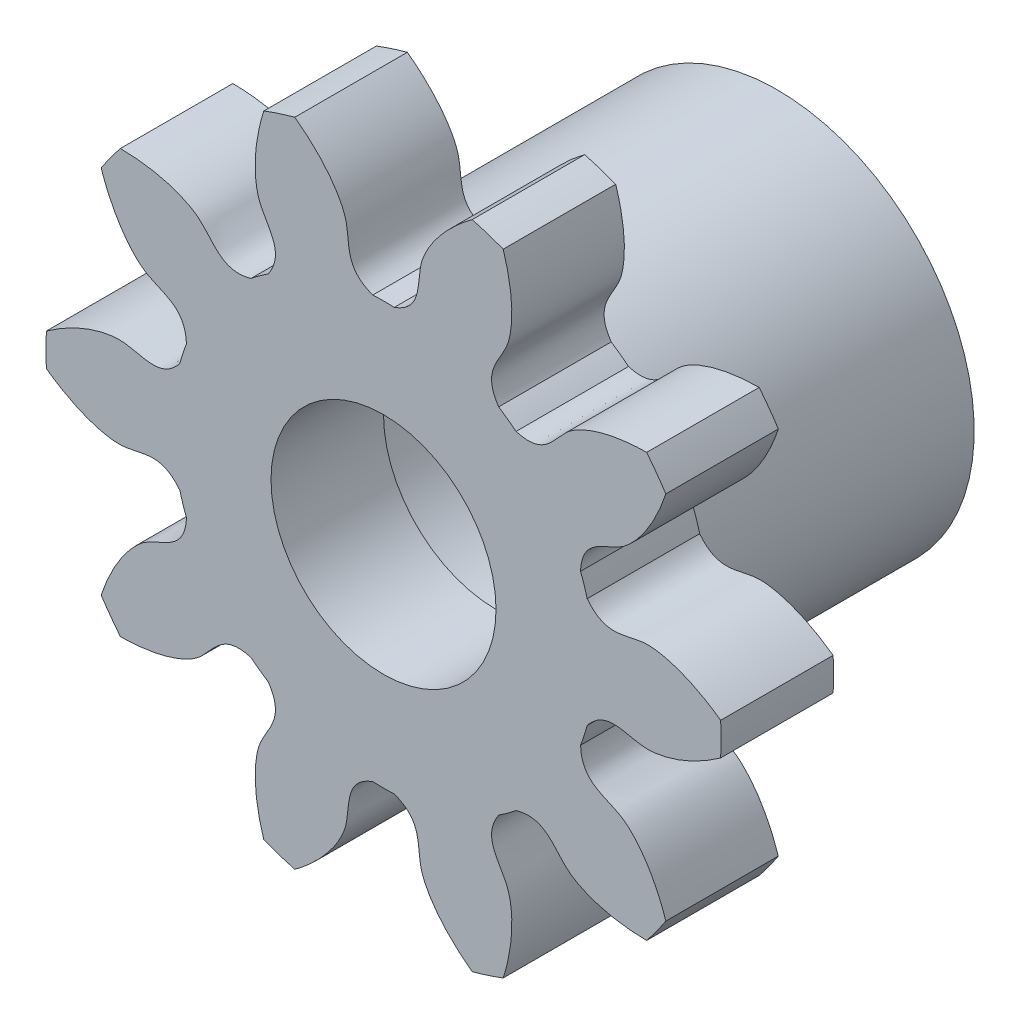
SolidWorks part; units mm, degrees
ref_plane "前视基准面" through (0, 0, 0) normal (0, 0, 1) x (1, 0, 0)
ref_plane "上视基准面" through (0, 0, 0) normal (0, 1, 0) x (1, 0, 0)
ref_plane "右视基准面" through (0, 0, 0) normal (1, 0, 0) x (0, 0, -1)
sketch "草图1" plane through (0, 0, 0) normal (0, 0, 1) x (1, 0, 0)
  circle A0 centre (0, 0) radius 12
extrude "凸台-拉伸1" add sketch "草图1" along normal blind 30
ref_axis "基准轴1" through (0, 0, -1.5) along (0, 0, 1)
sketch "草图2" plane through (0, 0, 0) normal (0, 0, 1) x (1, 0, 0)
  line L0 (0, 0) -> (0, 12) construction
  circle A0 centre (0, 0) radius 12 construction
  arc A1 (0.3809, 7.4903) -> (-0.3809, 7.4903) centre (0, 0) ccw
  arc A2 (8.5072, 13.3886) -> (-8.5072, 13.3886) centre (0, 0) ccw
  spline S0 degree 3 poles (0.3809, 7.4903) (1.4509, 7.8811) (1.1477, 8.7412) (1.3773, 9.4493) (1.389, 9.4831) (1.4027, 9.5201) (1.4184, 9.5604) (1.4364, 9.6038) (1.4568, 9.6502) (1.4797, 9.6997) (1.5052, 9.7521) (1.5335, 9.8073) (1.5646, 9.8653) (1.5987, 9.9258) (1.636, 9.989) (1.6765, 10.0545) (1.7203, 10.1225) (1.7675, 10.1926) (1.8184, 10.2648) (1.8728, 10.3391) (1.9311, 10.4152) (1.9932, 10.4931) (2.0592, 10.5726) (2.1293, 10.6537) (2.2035, 10.7361) (2.2819, 10.8197) (2.3646, 10.9045) (2.4516, 10.9902) (2.5431, 11.0768) (2.639, 11.164) (2.7395, 11.2518) (2.8447, 11.3399) (2.9545, 11.4283) (3.069, 11.5168) (3.1883, 11.6052) (3.3124, 11.6934) (3.4413, 11.7812) (3.5751, 11.8685) (3.7138, 11.9551) (3.8575, 12.0408) (4.0061, 12.1254) (4.1597, 12.2089) (4.3182, 12.291) (4.4818, 12.3716) (4.6503, 12.4505) (4.8238, 12.5275) (5.0022, 12.6025) (5.1856, 12.6753) (5.374, 12.7458) (5.5673, 12.8137) (5.7655, 12.8789) (5.9685, 12.9412) (6.1763, 13.0005) (6.389, 13.0566) (6.6063, 13.1093) (6.8284, 13.1585) (7.055, 13.2039) (7.2863, 13.2455) (7.522, 13.283) (7.7621, 13.3164) (8.0906, 13.3553) (8.3397, 13.3772) (8.5072, 13.3886) knots 0 0 0 0 0.201721 0.204697 0.208023 0.211699 0.215726 0.220102 0.224829 0.229906 0.235332 0.241109 0.247237 0.253714 0.260541 0.267719 0.275246 0.283124 0.291352 0.29993 0.308858 0.318136 0.327765 0.337743 0.348072 0.358751 0.36978 0.381158 0.392888 0.404967 0.417396 0.430176 0.443305 0.456785 0.470615 0.484795 0.499325 0.514205 0.529435 0.545016 0.560946 0.577227 0.593858 0.610839 0.62817 0.645851 0.663882 0.682264 0.700995 0.720077 0.739509 0.759291 0.779423 0.799905 0.820737 0.84192 0.863452 0.885335 0.907568 0.930151 0.953084 1 1 1 1
  spline S1 degree 3 poles (-0.3809, 7.4903) (-1.4509, 7.8811) (-1.1477, 8.7412) (-1.3773, 9.4493) (-1.389, 9.4831) (-1.4027, 9.5201) (-1.4184, 9.5604) (-1.4364, 9.6038) (-1.4568, 9.6502) (-1.4797, 9.6997) (-1.5052, 9.7521) (-1.5335, 9.8073) (-1.5646, 9.8653) (-1.5987, 9.9258) (-1.636, 9.989) (-1.6765, 10.0545) (-1.7203, 10.1225) (-1.7675, 10.1926) (-1.8184, 10.2648) (-1.8728, 10.3391) (-1.9311, 10.4152) (-1.9932, 10.4931) (-2.0592, 10.5726) (-2.1293, 10.6537) (-2.2035, 10.7361) (-2.2819, 10.8197) (-2.3646, 10.9045) (-2.4516, 10.9902) (-2.5431, 11.0768) (-2.639, 11.164) (-2.7395, 11.2518) (-2.8447, 11.3399) (-2.9545, 11.4283) (-3.069, 11.5168) (-3.1883, 11.6052) (-3.3124, 11.6934) (-3.4413, 11.7812) (-3.5751, 11.8685) (-3.7138, 11.9551) (-3.8575, 12.0408) (-4.0061, 12.1254) (-4.1597, 12.2089) (-4.3182, 12.291) (-4.4818, 12.3716) (-4.6503, 12.4505) (-4.8238, 12.5275) (-5.0022, 12.6025) (-5.1856, 12.6753) (-5.374, 12.7458) (-5.5673, 12.8137) (-5.7655, 12.8789) (-5.9685, 12.9412) (-6.1763, 13.0005) (-6.389, 13.0566) (-6.6063, 13.1093) (-6.8284, 13.1585) (-7.055, 13.2039) (-7.2863, 13.2455) (-7.522, 13.283) (-7.7621, 13.3164) (-8.0906, 13.3553) (-8.3397, 13.3772) (-8.5072, 13.3886) knots 0 0 0 0 0.201721 0.204697 0.208023 0.211699 0.215726 0.220102 0.224829 0.229906 0.235332 0.241109 0.247237 0.253714 0.260541 0.267719 0.275246 0.283124 0.291352 0.29993 0.308858 0.318136 0.327765 0.337743 0.348072 0.358751 0.36978 0.381158 0.392888 0.404967 0.417396 0.430176 0.443305 0.456785 0.470615 0.484795 0.499325 0.514205 0.529435 0.545016 0.560946 0.577227 0.593858 0.610839 0.62817 0.645851 0.663882 0.682264 0.700995 0.720077 0.739509 0.759291 0.779423 0.799905 0.820737 0.84192 0.863452 0.885335 0.907568 0.930151 0.953084 1 1 1 1
extrude "切除-拉伸1" cut sketch "草图2" along normal through all
pattern_circular "阵列(圆周)1" count 10 every 36 about axis through (0, 0, -1.5) along (0, 0, 1) of "切除-拉伸1"
sketch "草图3" plane through (0, 0, 0) normal (0, 0, 1) x (1, 0, 0)
  circle A0 centre (0, 0) radius 10 construction
  arc A21 (-4.0945, 6.2837) -> (-4.7109, 5.8359) centre (0, 0) ccw
  arc A22 (-9.3561, 7.5142) -> (-10.0376, 6.5762) centre (0, 0) ccw
  arc A23 (-7.006, 2.6769) -> (-7.2414, 1.9524) centre (0, 0) ccw
  arc A24 (-11.986, 0.5797) -> (-11.986, -0.5797) centre (0, 0) ccw
  arc A25 (-7.2414, -1.9524) -> (-7.006, -2.6769) centre (0, 0) ccw
  arc A26 (-10.0376, -6.5762) -> (-9.3561, -7.5142) centre (0, 0) ccw
  arc A27 (-4.7109, -5.8359) -> (-4.0945, -6.2837) centre (0, 0) ccw
  arc A28 (-4.2552, -11.2202) -> (-3.1525, -11.5785) centre (0, 0) ccw
  arc A29 (-0.3809, -7.4903) -> (0.3809, -7.4903) centre (0, 0) ccw
  arc A30 (3.1525, -11.5785) -> (4.2552, -11.2202) centre (0, 0) ccw
  arc A31 (4.0945, -6.2837) -> (4.7109, -5.8359) centre (0, 0) ccw
  arc A32 (9.3561, -7.5142) -> (10.0376, -6.5762) centre (0, 0) ccw
  arc A33 (7.006, -2.6769) -> (7.2414, -1.9524) centre (0, 0) ccw
  arc A34 (11.986, -0.5797) -> (11.986, 0.5797) centre (0, 0) ccw
  arc A35 (7.2414, 1.9524) -> (7.006, 2.6769) centre (0, 0) ccw
  arc A36 (10.0376, 6.5762) -> (9.3561, 7.5142) centre (0, 0) ccw
  arc A37 (4.7109, 5.8359) -> (4.0945, 6.2837) centre (0, 0) ccw
  arc A38 (4.2552, 11.2202) -> (3.1525, 11.5785) centre (0, 0) ccw
  arc A39 (0.3809, 7.4903) -> (-0.3809, 7.4903) centre (0, 0) ccw
  arc A40 (-3.1525, 11.5785) -> (-4.2552, 11.2202) centre (0, 0) ccw
  arc A41 (-4.0945, 6.2837) -> (-4.7109, 5.8359) centre (0, 0) ccw
  arc A42 (-9.3561, 7.5142) -> (-10.0376, 6.5762) centre (0, 0) ccw
  arc A43 (-7.006, 2.6769) -> (-7.2414, 1.9524) centre (0, 0) ccw
  arc A44 (-11.986, 0.5797) -> (-11.986, -0.5797) centre (0, 0) ccw
  arc A45 (-7.2414, -1.9524) -> (-7.006, -2.6769) centre (0, 0) ccw
  arc A46 (-10.0376, -6.5762) -> (-9.3561, -7.5142) centre (0, 0) ccw
  arc A47 (-4.7109, -5.8359) -> (-4.0945, -6.2837) centre (0, 0) ccw
  arc A48 (-4.2552, -11.2202) -> (-3.1525, -11.5785) centre (0, 0) ccw
  arc A49 (-0.3809, -7.4903) -> (0.3809, -7.4903) centre (0, 0) ccw
  arc A50 (3.1525, -11.5785) -> (4.2552, -11.2202) centre (0, 0) ccw
  arc A51 (4.0945, -6.2837) -> (4.7109, -5.8359) centre (0, 0) ccw
  arc A52 (9.3561, -7.5142) -> (10.0376, -6.5762) centre (0, 0) ccw
  arc A53 (7.006, -2.6769) -> (7.2414, -1.9524) centre (0, 0) ccw
  arc A54 (11.986, -0.5797) -> (11.986, 0.5797) centre (0, 0) ccw
  arc A55 (7.2414, 1.9524) -> (7.006, 2.6769) centre (0, 0) ccw
  arc A56 (10.0376, 6.5762) -> (9.3561, 7.5142) centre (0, 0) ccw
  arc A57 (4.7109, 5.8359) -> (4.0945, 6.2837) centre (0, 0) ccw
  arc A58 (4.2552, 11.2202) -> (3.1525, 11.5785) centre (0, 0) ccw
  arc A59 (0.3809, 7.4903) -> (-0.3809, 7.4903) centre (0, 0) ccw
  arc A60 (-3.1525, 11.5785) -> (-4.2552, 11.2202) centre (0, 0) ccw
  spline S20 degree 3 poles (2357.9896, 3233.0149) (-45.5111, -76.1208) (0.8912, 1.3359) (-6.6791, 6.8428) (-6.7335, 6.8799) (-6.81, 6.9276) (-6.9015, 6.9798) (-7.0083, 7.0352) (-7.1308, 7.0926) (-7.2694, 7.151) (-7.4243, 7.2091) (-7.5956, 7.2657) (-7.7836, 7.3195) (-7.9881, 7.3693) (-8.2093, 7.4139) (-8.4468, 7.452) (-8.7007, 7.4824) (-8.9705, 7.5038) (-41.9663, 8.7956) (-79.134, -211.6177) (2738.2164, 2912.7683) knots -1.870678 -1.870678 -1.870678 -1.870678 0.735149 0.738125 0.745127 0.75353 0.763333 0.774537 0.787142 0.801147 0.816552 0.833358 0.851564 0.871171 0.892178 0.914586 0.938395 0.963603 0.990213 10.164096 10.164096 10.164096 10.164096 only from (-4.7109, 5.8359) to (-9.3561, 7.5142)
  spline S21 degree 3 poles (-1900.4629, -3517.2649) (168.6597, 144.2035) (-22.0225, 35.4119) (-9.8048, 5.9626) (-9.6975, 5.7306) (-9.5878, 5.5164) (-9.4771, 5.3199) (-9.3665, 5.1408) (-9.2572, 4.9787) (-9.1505, 4.8332) (-9.0474, 4.7038) (-8.9491, 4.5901) (-8.8565, 4.4913) (-8.7709, 4.4068) (-8.693, 4.336) (-8.6239, 4.2779) (-8.5719, 4.2376) (-0.9951, -1.2604) (58.3315, 66.8063) (-2346.1255, -3241.6441) knots -8.822355 -8.822355 -8.822355 -8.822355 0.036397 0.061605 0.085414 0.107822 0.128829 0.148436 0.166642 0.183448 0.198853 0.212858 0.225463 0.236667 0.24647 0.254873 0.261875 0.264851 2.87068 2.87068 2.87068 2.87068 only from (-10.0376, 6.5762) to (-7.006, 2.6769)
  spline S22 degree 3 poles (7.3352, 4001.5555) (7.9234, -88.3337) (-0.0642, 1.6046) (-9.4256, 1.6101) (-9.4914, 1.6081) (-9.5814, 1.6018) (-9.686, 1.5902) (-9.805, 1.5722) (-9.9379, 1.5467) (-10.0843, 1.5125) (-10.2438, 1.4684) (-10.4157, 1.4134) (-10.5993, 1.3465) (-10.7941, 1.2666) (-10.9992, 1.1727) (-11.2138, 1.0639) (-11.437, 0.9392) (-11.6679, 0.7979) (-39.1213, -17.5514) (60.365, -217.7161) (503.1813, 3965.9623) knots -1.870678 -1.870678 -1.870678 -1.870678 0.735149 0.738125 0.745127 0.75353 0.763333 0.774537 0.787142 0.801147 0.816552 0.833358 0.851564 0.871171 0.892178 0.914586 0.938395 0.963603 0.990213 10.164096 10.164096 10.164096 10.164096 only from (-7.2414, 1.9524) to (-11.986, 0.5797)
  spline S23 degree 3 poles (529.8897, -3962.5911) (51.6878, 215.7988) (-38.6312, 15.7043) (-11.437, -0.9392) (-11.2138, -1.0639) (-10.9992, -1.1727) (-10.7941, -1.2666) (-10.5993, -1.3465) (-10.4157, -1.4134) (-10.2438, -1.4684) (-10.0843, -1.5125) (-9.9379, -1.5467) (-9.805, -1.5722) (-9.686, -1.5902) (-9.5814, -1.6018) (-9.4914, -1.6081) (-9.4256, -1.6101) (-0.0642, -1.6046) (7.9234, 88.3338) (7.3352, -4001.5632) knots -8.822355 -8.822355 -8.822355 -8.822355 0.036397 0.061605 0.085414 0.107822 0.128829 0.148436 0.166642 0.183448 0.198853 0.212858 0.225463 0.236667 0.24647 0.254873 0.261875 0.264851 2.87068 2.87068 2.87068 2.87068 only from (-11.986, -0.5797) to (-7.2414, -1.9524)
  spline S24 degree 3 poles (-2346.121, 3241.6379) (58.3315, -66.8062) (-0.9952, 1.2604) (-8.5719, -4.2376) (-8.6239, -4.2779) (-8.693, -4.336) (-8.7709, -4.4068) (-8.8565, -4.4913) (-8.9491, -4.5901) (-9.0474, -4.7038) (-9.1505, -4.8332) (-9.2572, -4.9787) (-9.3665, -5.1408) (-9.4771, -5.3199) (-9.5878, -5.5164) (-9.6975, -5.7306) (-9.8048, -5.9626) (-9.9085, -6.2127) (-21.3334, -37.1943) (176.8067, -140.6544) (-1924.0519, 3504.2934) knots -1.870678 -1.870678 -1.870678 -1.870678 0.735149 0.738125 0.745127 0.75353 0.763333 0.774537 0.787142 0.801147 0.816552 0.833358 0.851564 0.871171 0.892178 0.914586 0.938395 0.963603 0.990213 10.164096 10.164096 10.164096 10.164096 only from (-7.006, -2.6769) to (-10.0376, -6.5762)
  spline S25 degree 3 poles (2757.8424, -2894.3422) (-85.027, 204.9662) (-40.4841, -10.0018) (-8.7007, -7.4824) (-8.4468, -7.452) (-8.2093, -7.4139) (-7.9881, -7.3693) (-7.7836, -7.3195) (-7.5956, -7.2657) (-7.4243, -7.2091) (-7.2694, -7.151) (-7.1308, -7.0926) (-7.0083, -7.0352) (-6.9015, -6.9798) (-6.81, -6.9277) (-6.7335, -6.8799) (-6.6791, -6.8428) (0.8912, -1.3359) (-45.5111, 76.1209) (2357.9941, -3233.0211) knots -8.822355 -8.822355 -8.822355 -8.822355 0.036397 0.061605 0.085414 0.107822 0.128829 0.148436 0.166642 0.183448 0.198853 0.212858 0.225463 0.236667 0.24647 0.254873 0.261875 0.264851 2.87068 2.87068 2.87068 2.87068 only from (-9.3561, -7.5142) to (-4.7109, -5.8359)
  spline S26 degree 3 poles (-3803.4388, 1243.5248) (86.4588, -19.761) (-1.546, 0.4348) (-4.444, -8.4668) (-4.4624, -8.5299) (-4.4842, -8.6175) (-4.5055, -8.7206) (-4.5252, -8.8393) (-4.542, -8.9735) (-4.5547, -9.1234) (-4.562, -9.2886) (-4.5629, -9.4691) (-4.556, -9.6645) (-4.5402, -9.8744) (-4.5142, -10.0985) (-4.4771, -10.3362) (-4.4275, -10.587) (-4.3645, -10.8503) (4.6032, -42.6303) (225.7141, -9.8674) (-3616.3627, 1704.1036) knots -1.870678 -1.870678 -1.870678 -1.870678 0.735149 0.738125 0.745127 0.75353 0.763333 0.774537 0.787142 0.801147 0.816552 0.833358 0.851564 0.871171 0.892178 0.914586 0.938395 0.963603 0.990213 10.164096 10.164096 10.164096 10.164096 only from (-4.0945, -6.2837) to (-4.2552, -11.2202)
  spline S27 degree 3 poles (3932.393, -720.553) (-189.2644, 115.8435) (-26.8734, -31.8875) (-2.641, -11.1675) (-2.4534, -10.9937) (-2.2836, -10.8233) (-2.131, -10.6572) (-1.9948, -10.4967) (-1.8744, -10.3427) (-1.769, -10.1962) (-1.6778, -10.0581) (-1.6, -9.9295) (-1.5346, -9.8109) (-1.4808, -9.7034) (-1.4375, -9.6074) (-1.4036, -9.5238) (-1.3814, -9.4619) (1.5063, -0.5569) (-81.562, 34.8323) (3807.9794, -1229.5749) knots -8.822355 -8.822355 -8.822355 -8.822355 0.036397 0.061605 0.085414 0.107822 0.128829 0.148436 0.166642 0.183448 0.198853 0.212858 0.225463 0.236667 0.24647 0.254873 0.261875 0.264851 2.87068 2.87068 2.87068 2.87068 only from (-3.1525, -11.5785) to (-0.3809, -7.4903)
  spline S28 degree 3 poles (-3807.9721, -1229.5725) (81.5619, 34.8323) (-1.5063, -0.557) (1.3814, -9.4619) (1.4036, -9.5238) (1.4375, -9.6074) (1.4808, -9.7034) (1.5346, -9.8109) (1.6, -9.9295) (1.6778, -10.0581) (1.769, -10.1962) (1.8744, -10.3427) (1.9948, -10.4967) (2.131, -10.6572) (2.2836, -10.8233) (2.4534, -10.9937) (2.641, -11.1675) (2.8467, -11.3434) (28.7815, -31.7829) (188.4065, 124.6885) (-3927.3458, -746.9958) knots -1.870678 -1.870678 -1.870678 -1.870678 0.735149 0.738125 0.745127 0.75353 0.763333 0.774537 0.787142 0.801147 0.816552 0.833358 0.851564 0.871171 0.892178 0.914586 0.938395 0.963603 0.990213 10.164096 10.164096 10.164096 10.164096 only from (0.3809, -7.4903) to (3.1525, -11.5785)
  spline S29 degree 3 poles (3604.9032, 1728.463) (-221.2093, -17.5274) (-2.998, -41.5933) (4.4275, -10.587) (4.4771, -10.3362) (4.5142, -10.0985) (4.5402, -9.8744) (4.556, -9.6645) (4.5629, -9.4691) (4.562, -9.2886) (4.5547, -9.1234) (4.542, -8.9735) (4.5252, -8.8393) (4.5055, -8.7206) (4.4842, -8.6175) (4.4624, -8.5299) (4.444, -8.4668) (1.5459, 0.4348) (-86.459, -19.761) (3803.446, 1243.5272) knots -8.822355 -8.822355 -8.822355 -8.822355 0.036397 0.061605 0.085414 0.107822 0.128829 0.148436 0.166642 0.183448 0.198853 0.212858 0.225463 0.236667 0.24647 0.254873 0.261875 0.264851 2.87068 2.87068 2.87068 2.87068 only from (4.2552, -11.2202) to (4.0945, -6.2837)
  spline S30 degree 3 poles (-2357.9896, -3233.0149) (45.5111, 76.1208) (-0.8912, -1.3359) (6.6791, -6.8428) (6.7335, -6.8799) (6.81, -6.9276) (6.9015, -6.9798) (7.0083, -7.0352) (7.1308, -7.0926) (7.2694, -7.151) (7.4243, -7.2091) (7.5956, -7.2657) (7.7836, -7.3195) (7.9881, -7.3693) (8.2093, -7.4139) (8.4468, -7.452) (8.7007, -7.4824) (8.9705, -7.5038) (41.9663, -8.7956) (79.134, 211.6177) (-2738.2164, -2912.7683) knots -1.870678 -1.870678 -1.870678 -1.870678 0.735149 0.738125 0.745127 0.75353 0.763333 0.774537 0.787142 0.801147 0.816552 0.833358 0.851564 0.871171 0.892178 0.914586 0.938395 0.963603 0.990213 10.164096 10.164096 10.164096 10.164096 only from (4.7109, -5.8359) to (9.3561, -7.5142)
  spline S31 degree 3 poles (1900.4629, 3517.2649) (-168.6597, -144.2035) (22.0225, -35.4119) (9.8048, -5.9626) (9.6975, -5.7306) (9.5878, -5.5164) (9.4771, -5.3199) (9.3665, -5.1408) (9.2572, -4.9787) (9.1505, -4.8332) (9.0474, -4.7038) (8.9491, -4.5901) (8.8565, -4.4913) (8.7709, -4.4068) (8.693, -4.336) (8.6239, -4.2779) (8.5719, -4.2376) (0.9951, 1.2604) (-58.3315, -66.8063) (2346.1255, 3241.6441) knots -8.822355 -8.822355 -8.822355 -8.822355 0.036397 0.061605 0.085414 0.107822 0.128829 0.148436 0.166642 0.183448 0.198853 0.212858 0.225463 0.236667 0.24647 0.254873 0.261875 0.264851 2.87068 2.87068 2.87068 2.87068 only from (10.0376, -6.5762) to (7.006, -2.6769)
  spline S32 degree 3 poles (-7.3352, -4001.5555) (-7.9234, 88.3337) (0.0642, -1.6046) (9.4256, -1.6101) (9.4914, -1.6081) (9.5814, -1.6018) (9.686, -1.5902) (9.805, -1.5722) (9.9379, -1.5467) (10.0843, -1.5125) (10.2438, -1.4684) (10.4157, -1.4134) (10.5993, -1.3465) (10.7941, -1.2666) (10.9992, -1.1727) (11.2138, -1.0639) (11.437, -0.9392) (11.6679, -0.7979) (39.1213, 17.5514) (-60.365, 217.7161) (-503.1813, -3965.9623) knots -1.870678 -1.870678 -1.870678 -1.870678 0.735149 0.738125 0.745127 0.75353 0.763333 0.774537 0.787142 0.801147 0.816552 0.833358 0.851564 0.871171 0.892178 0.914586 0.938395 0.963603 0.990213 10.164096 10.164096 10.164096 10.164096 only from (7.2414, -1.9524) to (11.986, -0.5797)
  spline S33 degree 3 poles (-529.8897, 3962.5911) (-51.6878, -215.7988) (38.6312, -15.7043) (11.437, 0.9392) (11.2138, 1.0639) (10.9992, 1.1727) (10.7941, 1.2666) (10.5993, 1.3465) (10.4157, 1.4134) (10.2438, 1.4684) (10.0843, 1.5125) (9.9379, 1.5467) (9.805, 1.5722) (9.686, 1.5902) (9.5814, 1.6018) (9.4914, 1.6081) (9.4256, 1.6101) (0.0642, 1.6046) (-7.9234, -88.3338) (-7.3352, 4001.5632) knots -8.822355 -8.822355 -8.822355 -8.822355 0.036397 0.061605 0.085414 0.107822 0.128829 0.148436 0.166642 0.183448 0.198853 0.212858 0.225463 0.236667 0.24647 0.254873 0.261875 0.264851 2.87068 2.87068 2.87068 2.87068 only from (11.986, 0.5797) to (7.2414, 1.9524)
  spline S34 degree 3 poles (2346.121, -3241.6379) (-58.3315, 66.8062) (0.9952, -1.2604) (8.5719, 4.2376) (8.6239, 4.2779) (8.693, 4.336) (8.7709, 4.4068) (8.8565, 4.4913) (8.9491, 4.5901) (9.0474, 4.7038) (9.1505, 4.8332) (9.2572, 4.9787) (9.3665, 5.1408) (9.4771, 5.3199) (9.5878, 5.5164) (9.6975, 5.7306) (9.8048, 5.9626) (9.9085, 6.2127) (21.3334, 37.1943) (-176.8067, 140.6544) (1924.0519, -3504.2934) knots -1.870678 -1.870678 -1.870678 -1.870678 0.735149 0.738125 0.745127 0.75353 0.763333 0.774537 0.787142 0.801147 0.816552 0.833358 0.851564 0.871171 0.892178 0.914586 0.938395 0.963603 0.990213 10.164096 10.164096 10.164096 10.164096 only from (7.006, 2.6769) to (10.0376, 6.5762)
  spline S35 degree 3 poles (-2757.8424, 2894.3422) (85.027, -204.9662) (40.4841, 10.0018) (8.7007, 7.4824) (8.4468, 7.452) (8.2093, 7.4139) (7.9881, 7.3693) (7.7836, 7.3195) (7.5956, 7.2657) (7.4243, 7.2091) (7.2694, 7.151) (7.1308, 7.0926) (7.0083, 7.0352) (6.9015, 6.9798) (6.81, 6.9277) (6.7335, 6.8799) (6.6791, 6.8428) (-0.8912, 1.3359) (45.5111, -76.1209) (-2357.9941, 3233.0211) knots -8.822355 -8.822355 -8.822355 -8.822355 0.036397 0.061605 0.085414 0.107822 0.128829 0.148436 0.166642 0.183448 0.198853 0.212858 0.225463 0.236667 0.24647 0.254873 0.261875 0.264851 2.87068 2.87068 2.87068 2.87068 only from (9.3561, 7.5142) to (4.7109, 5.8359)
  spline S36 degree 3 poles (3803.4388, -1243.5248) (-86.4588, 19.761) (1.546, -0.4348) (4.444, 8.4668) (4.4624, 8.5299) (4.4842, 8.6175) (4.5055, 8.7206) (4.5252, 8.8393) (4.542, 8.9735) (4.5547, 9.1234) (4.562, 9.2886) (4.5629, 9.4691) (4.556, 9.6645) (4.5402, 9.8744) (4.5142, 10.0985) (4.4771, 10.3362) (4.4275, 10.587) (4.3645, 10.8503) (-4.6032, 42.6303) (-225.7141, 9.8674) (3616.3627, -1704.1036) knots -1.870678 -1.870678 -1.870678 -1.870678 0.735149 0.738125 0.745127 0.75353 0.763333 0.774537 0.787142 0.801147 0.816552 0.833358 0.851564 0.871171 0.892178 0.914586 0.938395 0.963603 0.990213 10.164096 10.164096 10.164096 10.164096 only from (4.0945, 6.2837) to (4.2552, 11.2202)
  spline S37 degree 3 poles (-3932.393, 720.553) (189.2644, -115.8435) (26.8734, 31.8875) (2.641, 11.1675) (2.4534, 10.9937) (2.2836, 10.8233) (2.131, 10.6572) (1.9948, 10.4967) (1.8744, 10.3427) (1.769, 10.1962) (1.6778, 10.0581) (1.6, 9.9295) (1.5346, 9.8109) (1.4808, 9.7034) (1.4375, 9.6074) (1.4036, 9.5238) (1.3814, 9.4619) (-1.5063, 0.5569) (81.562, -34.8323) (-3807.9794, 1229.5749) knots -8.822355 -8.822355 -8.822355 -8.822355 0.036397 0.061605 0.085414 0.107822 0.128829 0.148436 0.166642 0.183448 0.198853 0.212858 0.225463 0.236667 0.24647 0.254873 0.261875 0.264851 2.87068 2.87068 2.87068 2.87068 only from (3.1525, 11.5785) to (0.3809, 7.4903)
  spline S38 degree 3 poles (3807.9721, 1229.5725) (-81.5619, -34.8323) (1.5063, 0.557) (-1.3814, 9.4619) (-1.4036, 9.5238) (-1.4375, 9.6074) (-1.4808, 9.7034) (-1.5346, 9.8109) (-1.6, 9.9295) (-1.6778, 10.0581) (-1.769, 10.1962) (-1.8744, 10.3427) (-1.9948, 10.4967) (-2.131, 10.6572) (-2.2836, 10.8233) (-2.4534, 10.9937) (-2.641, 11.1675) (-2.8467, 11.3434) (-28.7815, 31.7829) (-188.4065, -124.6885) (3927.3458, 746.9958) knots -1.870678 -1.870678 -1.870678 -1.870678 0.735149 0.738125 0.745127 0.75353 0.763333 0.774537 0.787142 0.801147 0.816552 0.833358 0.851564 0.871171 0.892178 0.914586 0.938395 0.963603 0.990213 10.164096 10.164096 10.164096 10.164096 only from (-0.3809, 7.4903) to (-3.1525, 11.5785)
  spline S39 degree 3 poles (-3604.9032, -1728.463) (221.2093, 17.5274) (2.998, 41.5933) (-4.4275, 10.587) (-4.4771, 10.3362) (-4.5142, 10.0985) (-4.5402, 9.8744) (-4.556, 9.6645) (-4.5629, 9.4691) (-4.562, 9.2886) (-4.5547, 9.1234) (-4.542, 8.9735) (-4.5252, 8.8393) (-4.5055, 8.7206) (-4.4842, 8.6175) (-4.4624, 8.5299) (-4.444, 8.4668) (-1.5459, -0.4348) (86.459, 19.761) (-3803.446, -1243.5272) knots -8.822355 -8.822355 -8.822355 -8.822355 0.036397 0.061605 0.085414 0.107822 0.128829 0.148436 0.166642 0.183448 0.198853 0.212858 0.225463 0.236667 0.24647 0.254873 0.261875 0.264851 2.87068 2.87068 2.87068 2.87068 only from (-4.2552, 11.2202) to (-4.0945, 6.2837)
  spline S40 degree 3 poles (-4.7109, 5.8359) (-5.8062, 5.5232) (-6.0664, 6.3972) (-6.6791, 6.8428) (-6.7335, 6.8799) (-6.81, 6.9276) (-6.9015, 6.9798) (-7.0083, 7.0352) (-7.1308, 7.0926) (-7.2694, 7.151) (-7.4243, 7.2091) (-7.5956, 7.2657) (-7.7836, 7.3195) (-7.9881, 7.3693) (-8.2093, 7.4139) (-8.4468, 7.452) (-8.7007, 7.4824) (-8.9705, 7.5038) (-9.1908, 7.5124) (-9.3211, 7.514) (-9.3561, 7.5142) knots 0.533428 0.533428 0.533428 0.533428 0.735149 0.738125 0.745127 0.75353 0.763333 0.774537 0.787142 0.801147 0.816552 0.833358 0.851564 0.871171 0.892178 0.914586 0.938395 0.963603 0.990213 1 1 1 1
  spline S41 degree 3 poles (-10.0376, 6.5762) (-9.9967, 6.4525) (-9.922, 6.245) (-9.8048, 5.9626) (-9.6975, 5.7306) (-9.5878, 5.5164) (-9.4771, 5.3199) (-9.3665, 5.1408) (-9.2572, 4.9787) (-9.1505, 4.8332) (-9.0474, 4.7038) (-8.9491, 4.5901) (-8.8565, 4.4913) (-8.7709, 4.4068) (-8.693, 4.336) (-8.6239, 4.2779) (-8.5719, 4.2376) (-7.9587, 3.7927) (-7.0471, 3.8153) (-7.006, 2.6769) knots 0 0 0 0 0.036397 0.061605 0.085414 0.107822 0.128829 0.148436 0.166642 0.183448 0.198853 0.212858 0.225463 0.236667 0.24647 0.254873 0.261875 0.264851 0.466572 0.466572 0.466572 0.466572
  spline S42 degree 3 poles (-7.2414, 1.9524) (-7.9437, 1.0556) (-8.668, 1.6097) (-9.4256, 1.6101) (-9.4914, 1.6081) (-9.5814, 1.6018) (-9.686, 1.5902) (-9.805, 1.5722) (-9.9379, 1.5467) (-10.0843, 1.5125) (-10.2438, 1.4684) (-10.4157, 1.4134) (-10.5993, 1.3465) (-10.7941, 1.2666) (-10.9992, 1.1727) (-11.2138, 1.0639) (-11.437, 0.9392) (-11.6679, 0.7979) (-11.8512, 0.6754) (-11.9575, 0.6002) (-11.986, 0.5797) knots 0.533428 0.533428 0.533428 0.533428 0.735149 0.738125 0.745127 0.75353 0.763333 0.774537 0.787142 0.801147 0.816552 0.833358 0.851564 0.871171 0.892178 0.914586 0.938395 0.963603 0.990213 1 1 1 1
  spline S43 degree 3 poles (-11.986, -0.5797) (-11.8802, -0.6557) (-11.6978, -0.7797) (-11.437, -0.9392) (-11.2138, -1.0639) (-10.9992, -1.1727) (-10.7941, -1.2666) (-10.5993, -1.3465) (-10.4157, -1.4134) (-10.2438, -1.4684) (-10.0843, -1.5125) (-9.9379, -1.5467) (-9.805, -1.5722) (-9.686, -1.5902) (-9.5814, -1.6018) (-9.4914, -1.6081) (-9.4256, -1.6101) (-8.668, -1.6097) (-7.9437, -1.0556) (-7.2414, -1.9524) knots 0 0 0 0 0.036397 0.061605 0.085414 0.107822 0.128829 0.148436 0.166642 0.183448 0.198853 0.212858 0.225463 0.236667 0.24647 0.254873 0.261875 0.264851 0.466572 0.466572 0.466572 0.466572
  spline S44 degree 3 poles (-7.006, -2.6769) (-7.0471, -3.8153) (-7.9587, -3.7927) (-8.5719, -4.2376) (-8.6239, -4.2779) (-8.693, -4.336) (-8.7709, -4.4068) (-8.8565, -4.4913) (-8.9491, -4.5901) (-9.0474, -4.7038) (-9.1505, -4.8332) (-9.2572, -4.9787) (-9.3665, -5.1408) (-9.4771, -5.3199) (-9.5878, -5.5164) (-9.6975, -5.7306) (-9.8048, -5.9626) (-9.9085, -6.2127) (-9.9848, -6.4196) (-10.0266, -6.5429) (-10.0376, -6.5762) knots 0.533428 0.533428 0.533428 0.533428 0.735149 0.738125 0.745127 0.75353 0.763333 0.774537 0.787142 0.801147 0.816552 0.833358 0.851564 0.871171 0.892178 0.914586 0.938395 0.963603 0.990213 1 1 1 1
  spline S45 degree 3 poles (-9.3561, -7.5142) (-9.2259, -7.5135) (-9.0054, -7.5065) (-8.7007, -7.4824) (-8.4468, -7.452) (-8.2093, -7.4139) (-7.9881, -7.3693) (-7.7836, -7.3195) (-7.5956, -7.2657) (-7.4243, -7.2091) (-7.2694, -7.151) (-7.1308, -7.0926) (-7.0083, -7.0352) (-6.9015, -6.9798) (-6.81, -6.9277) (-6.7335, -6.8799) (-6.6791, -6.8428) (-6.0664, -6.3972) (-5.8062, -5.5232) (-4.7109, -5.8359) knots 0 0 0 0 0.036397 0.061605 0.085414 0.107822 0.128829 0.148436 0.166642 0.183448 0.198853 0.212858 0.225463 0.236667 0.24647 0.254873 0.261875 0.264851 0.466572 0.466572 0.466572 0.466572
  spline S46 degree 3 poles (-4.0945, -6.2837) (-3.4586, -7.2288) (-4.2094, -7.7464) (-4.444, -8.4668) (-4.4624, -8.5299) (-4.4842, -8.6175) (-4.5055, -8.7206) (-4.5252, -8.8393) (-4.542, -8.9735) (-4.5547, -9.1234) (-4.562, -9.2886) (-4.5629, -9.4691) (-4.556, -9.6645) (-4.5402, -9.8744) (-4.5142, -10.0985) (-4.4771, -10.3362) (-4.4275, -10.587) (-4.3645, -10.8503) (-4.3046, -11.0625) (-4.2659, -11.1868) (-4.2552, -11.2202) knots 0.533428 0.533428 0.533428 0.533428 0.735149 0.738125 0.745127 0.75353 0.763333 0.774537 0.787142 0.801147 0.816552 0.833358 0.851564 0.871171 0.892178 0.914586 0.938395 0.963603 0.990213 1 1 1 1
  spline S47 degree 3 poles (-3.1525, -11.5785) (-3.0476, -11.5014) (-2.8733, -11.3662) (-2.641, -11.1675) (-2.4534, -10.9937) (-2.2836, -10.8233) (-2.131, -10.6572) (-1.9948, -10.4967) (-1.8744, -10.3427) (-1.769, -10.1962) (-1.6778, -10.0581) (-1.6, -9.9295) (-1.5346, -9.8109) (-1.4808, -9.7034) (-1.4375, -9.6074) (-1.4036, -9.5238) (-1.3814, -9.4619) (-1.1477, -8.7412) (-1.4509, -7.8811) (-0.3809, -7.4903) knots 0 0 0 0 0.036397 0.061605 0.085414 0.107822 0.128829 0.148436 0.166642 0.183448 0.198853 0.212858 0.225463 0.236667 0.24647 0.254873 0.261875 0.264851 0.466572 0.466572 0.466572 0.466572
  spline S48 degree 3 poles (0.3809, -7.4903) (1.4509, -7.8811) (1.1477, -8.7412) (1.3814, -9.4619) (1.4036, -9.5238) (1.4375, -9.6074) (1.4808, -9.7034) (1.5346, -9.8109) (1.6, -9.9295) (1.6778, -10.0581) (1.769, -10.1962) (1.8744, -10.3427) (1.9948, -10.4967) (2.131, -10.6572) (2.2836, -10.8233) (2.4534, -10.9937) (2.641, -11.1675) (2.8467, -11.3434) (3.0199, -11.4799) (3.1243, -11.5578) (3.1525, -11.5785) knots 0.533428 0.533428 0.533428 0.533428 0.735149 0.738125 0.745127 0.75353 0.763333 0.774537 0.787142 0.801147 0.816552 0.833358 0.851564 0.871171 0.892178 0.914586 0.938395 0.963603 0.990213 1 1 1 1
  spline S49 degree 3 poles (4.2552, -11.2202) (4.2948, -11.0961) (4.3563, -10.8843) (4.4275, -10.587) (4.4771, -10.3362) (4.5142, -10.0985) (4.5402, -9.8744) (4.556, -9.6645) (4.5629, -9.4691) (4.562, -9.2886) (4.5547, -9.1234) (4.542, -8.9735) (4.5252, -8.8393) (4.5055, -8.7206) (4.4842, -8.6175) (4.4624, -8.5299) (4.444, -8.4668) (4.2094, -7.7464) (3.4586, -7.2288) (4.0945, -6.2837) knots 0 0 0 0 0.036397 0.061605 0.085414 0.107822 0.128829 0.148436 0.166642 0.183448 0.198853 0.212858 0.225463 0.236667 0.24647 0.254873 0.261875 0.264851 0.466572 0.466572 0.466572 0.466572
  spline S50 degree 3 poles (4.7109, -5.8359) (5.8062, -5.5232) (6.0664, -6.3972) (6.6791, -6.8428) (6.7335, -6.8799) (6.81, -6.9276) (6.9015, -6.9798) (7.0083, -7.0352) (7.1308, -7.0926) (7.2694, -7.151) (7.4243, -7.2091) (7.5956, -7.2657) (7.7836, -7.3195) (7.9881, -7.3693) (8.2093, -7.4139) (8.4468, -7.452) (8.7007, -7.4824) (8.9705, -7.5038) (9.1908, -7.5124) (9.3211, -7.514) (9.3561, -7.5142) knots 0.533428 0.533428 0.533428 0.533428 0.735149 0.738125 0.745127 0.75353 0.763333 0.774537 0.787142 0.801147 0.816552 0.833358 0.851564 0.871171 0.892178 0.914586 0.938395 0.963603 0.990213 1 1 1 1
  spline S51 degree 3 poles (10.0376, -6.5762) (9.9967, -6.4525) (9.922, -6.245) (9.8048, -5.9626) (9.6975, -5.7306) (9.5878, -5.5164) (9.4771, -5.3199) (9.3665, -5.1408) (9.2572, -4.9787) (9.1505, -4.8332) (9.0474, -4.7038) (8.9491, -4.5901) (8.8565, -4.4913) (8.7709, -4.4068) (8.693, -4.336) (8.6239, -4.2779) (8.5719, -4.2376) (7.9587, -3.7927) (7.0471, -3.8153) (7.006, -2.6769) knots 0 0 0 0 0.036397 0.061605 0.085414 0.107822 0.128829 0.148436 0.166642 0.183448 0.198853 0.212858 0.225463 0.236667 0.24647 0.254873 0.261875 0.264851 0.466572 0.466572 0.466572 0.466572
  spline S52 degree 3 poles (7.2414, -1.9524) (7.9437, -1.0556) (8.668, -1.6097) (9.4256, -1.6101) (9.4914, -1.6081) (9.5814, -1.6018) (9.686, -1.5902) (9.805, -1.5722) (9.9379, -1.5467) (10.0843, -1.5125) (10.2438, -1.4684) (10.4157, -1.4134) (10.5993, -1.3465) (10.7941, -1.2666) (10.9992, -1.1727) (11.2138, -1.0639) (11.437, -0.9392) (11.6679, -0.7979) (11.8512, -0.6754) (11.9575, -0.6002) (11.986, -0.5797) knots 0.533428 0.533428 0.533428 0.533428 0.735149 0.738125 0.745127 0.75353 0.763333 0.774537 0.787142 0.801147 0.816552 0.833358 0.851564 0.871171 0.892178 0.914586 0.938395 0.963603 0.990213 1 1 1 1
  spline S53 degree 3 poles (11.986, 0.5797) (11.8802, 0.6557) (11.6978, 0.7797) (11.437, 0.9392) (11.2138, 1.0639) (10.9992, 1.1727) (10.7941, 1.2666) (10.5993, 1.3465) (10.4157, 1.4134) (10.2438, 1.4684) (10.0843, 1.5125) (9.9379, 1.5467) (9.805, 1.5722) (9.686, 1.5902) (9.5814, 1.6018) (9.4914, 1.6081) (9.4256, 1.6101) (8.668, 1.6097) (7.9437, 1.0556) (7.2414, 1.9524) knots 0 0 0 0 0.036397 0.061605 0.085414 0.107822 0.128829 0.148436 0.166642 0.183448 0.198853 0.212858 0.225463 0.236667 0.24647 0.254873 0.261875 0.264851 0.466572 0.466572 0.466572 0.466572
  spline S54 degree 3 poles (7.006, 2.6769) (7.0471, 3.8153) (7.9587, 3.7927) (8.5719, 4.2376) (8.6239, 4.2779) (8.693, 4.336) (8.7709, 4.4068) (8.8565, 4.4913) (8.9491, 4.5901) (9.0474, 4.7038) (9.1505, 4.8332) (9.2572, 4.9787) (9.3665, 5.1408) (9.4771, 5.3199) (9.5878, 5.5164) (9.6975, 5.7306) (9.8048, 5.9626) (9.9085, 6.2127) (9.9848, 6.4196) (10.0266, 6.5429) (10.0376, 6.5762) knots 0.533428 0.533428 0.533428 0.533428 0.735149 0.738125 0.745127 0.75353 0.763333 0.774537 0.787142 0.801147 0.816552 0.833358 0.851564 0.871171 0.892178 0.914586 0.938395 0.963603 0.990213 1 1 1 1
  spline S55 degree 3 poles (9.3561, 7.5142) (9.2259, 7.5135) (9.0054, 7.5065) (8.7007, 7.4824) (8.4468, 7.452) (8.2093, 7.4139) (7.9881, 7.3693) (7.7836, 7.3195) (7.5956, 7.2657) (7.4243, 7.2091) (7.2694, 7.151) (7.1308, 7.0926) (7.0083, 7.0352) (6.9015, 6.9798) (6.81, 6.9277) (6.7335, 6.8799) (6.6791, 6.8428) (6.0664, 6.3972) (5.8062, 5.5232) (4.7109, 5.8359) knots 0 0 0 0 0.036397 0.061605 0.085414 0.107822 0.128829 0.148436 0.166642 0.183448 0.198853 0.212858 0.225463 0.236667 0.24647 0.254873 0.261875 0.264851 0.466572 0.466572 0.466572 0.466572
  spline S56 degree 3 poles (4.0945, 6.2837) (3.4586, 7.2288) (4.2094, 7.7464) (4.444, 8.4668) (4.4624, 8.5299) (4.4842, 8.6175) (4.5055, 8.7206) (4.5252, 8.8393) (4.542, 8.9735) (4.5547, 9.1234) (4.562, 9.2886) (4.5629, 9.4691) (4.556, 9.6645) (4.5402, 9.8744) (4.5142, 10.0985) (4.4771, 10.3362) (4.4275, 10.587) (4.3645, 10.8503) (4.3046, 11.0625) (4.2659, 11.1868) (4.2552, 11.2202) knots 0.533428 0.533428 0.533428 0.533428 0.735149 0.738125 0.745127 0.75353 0.763333 0.774537 0.787142 0.801147 0.816552 0.833358 0.851564 0.871171 0.892178 0.914586 0.938395 0.963603 0.990213 1 1 1 1
  spline S57 degree 3 poles (3.1525, 11.5785) (3.0476, 11.5014) (2.8733, 11.3662) (2.641, 11.1675) (2.4534, 10.9937) (2.2836, 10.8233) (2.131, 10.6572) (1.9948, 10.4967) (1.8744, 10.3427) (1.769, 10.1962) (1.6778, 10.0581) (1.6, 9.9295) (1.5346, 9.8109) (1.4808, 9.7034) (1.4375, 9.6074) (1.4036, 9.5238) (1.3814, 9.4619) (1.1477, 8.7412) (1.4509, 7.8811) (0.3809, 7.4903) knots 0 0 0 0 0.036397 0.061605 0.085414 0.107822 0.128829 0.148436 0.166642 0.183448 0.198853 0.212858 0.225463 0.236667 0.24647 0.254873 0.261875 0.264851 0.466572 0.466572 0.466572 0.466572
  spline S58 degree 3 poles (-0.3809, 7.4903) (-1.4509, 7.8811) (-1.1477, 8.7412) (-1.3814, 9.4619) (-1.4036, 9.5238) (-1.4375, 9.6074) (-1.4808, 9.7034) (-1.5346, 9.8109) (-1.6, 9.9295) (-1.6778, 10.0581) (-1.769, 10.1962) (-1.8744, 10.3427) (-1.9948, 10.4967) (-2.131, 10.6572) (-2.2836, 10.8233) (-2.4534, 10.9937) (-2.641, 11.1675) (-2.8467, 11.3434) (-3.0199, 11.4799) (-3.1243, 11.5578) (-3.1525, 11.5785) knots 0.533428 0.533428 0.533428 0.533428 0.735149 0.738125 0.745127 0.75353 0.763333 0.774537 0.787142 0.801147 0.816552 0.833358 0.851564 0.871171 0.892178 0.914586 0.938395 0.963603 0.990213 1 1 1 1
  spline S59 degree 3 poles (-4.2552, 11.2202) (-4.2948, 11.0961) (-4.3563, 10.8843) (-4.4275, 10.587) (-4.4771, 10.3362) (-4.5142, 10.0985) (-4.5402, 9.8744) (-4.556, 9.6645) (-4.5629, 9.4691) (-4.562, 9.2886) (-4.5547, 9.1234) (-4.542, 8.9735) (-4.5252, 8.8393) (-4.5055, 8.7206) (-4.4842, 8.6175) (-4.4624, 8.5299) (-4.444, 8.4668) (-4.2094, 7.7464) (-3.4586, 7.2288) (-4.0945, 6.2837) knots 0 0 0 0 0.036397 0.061605 0.085414 0.107822 0.128829 0.148436 0.166642 0.183448 0.198853 0.212858 0.225463 0.236667 0.24647 0.254873 0.261875 0.264851 0.466572 0.466572 0.466572 0.466572
  dimension "Dn" = 20
  dimension "D1" = 0
extrude "切除-拉伸2" cut sketch "草图3" along normal blind 26
sketch "草图4" plane through (0, 0, 26) normal (0, 0, -1) x (-1, 0, 0)
  line L3 (0, -1000) -> (0, 49000) construction
  line L4 (-1000, 0) -> (49000, 0) construction
  circle A2 centre (0, 0) radius 7
  circle A3 centre (0, 0) radius 5
  point P0 (0, 0)
  dimension "D1" = 14
  dimension "D2" = 10
extrude "凸台-拉伸2" add sketch "草图4" along normal blind 10
sketch "草图5" plane through (0, 0, 30) normal (0, 0, 1) x (1, 0, 0)
  circle A0 centre (0, 0) radius 4
  dimension "D1" = 8
extrude "切除-拉伸3" cut sketch "草图5" against normal up to next
